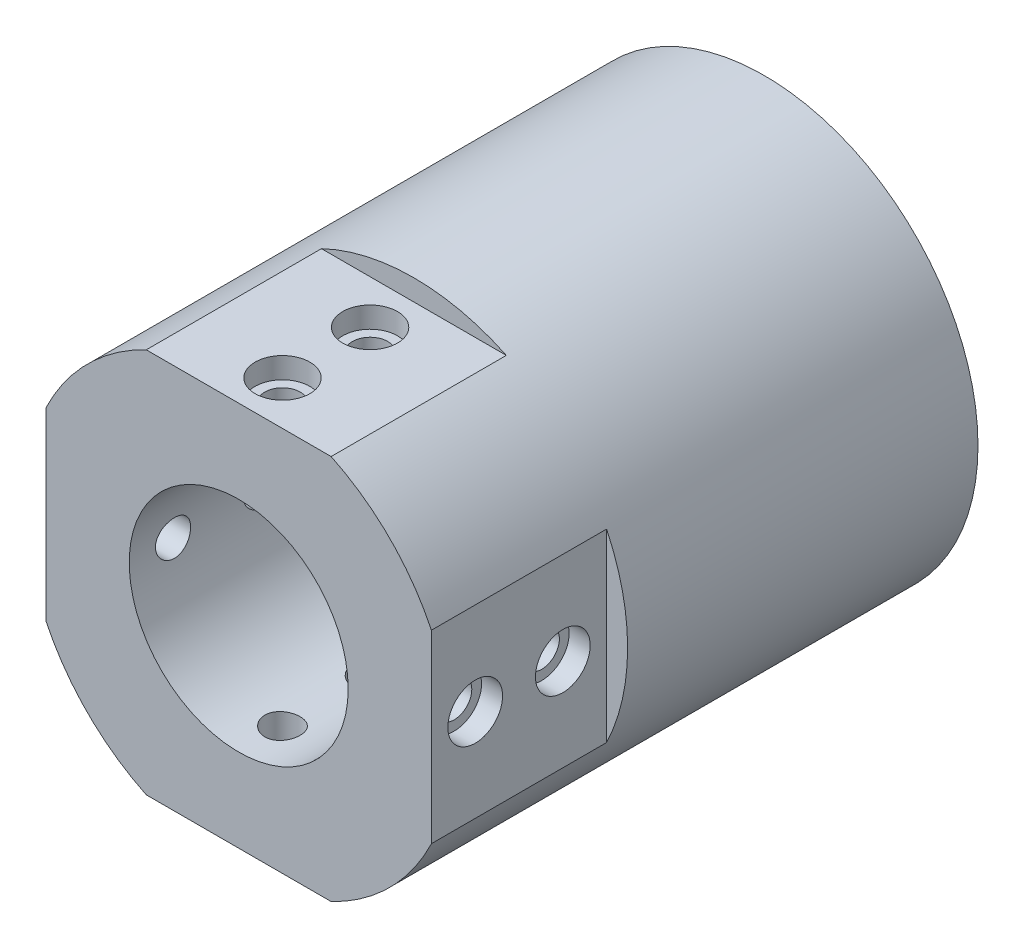
SolidWorks part; units mm, degrees
material "Brass"
ref_plane "Front Plane" through (0, 0, 0) normal (0, 0, 1) x (1, 0, 0)
ref_plane "Top Plane" through (0, 0, 0) normal (0, 1, 0) x (1, 0, 0)
ref_plane "Right Plane" through (0, 0, 0) normal (1, 0, 0) x (0, 0, -1)
sketch "Sketch1" plane through (0, 0, 0) normal (0, 0, 1) x (1, 0, 0)
  circle A0 centre (0, 0) radius 30.988
extrude "Boss-Extrude1" add sketch "Sketch1" along normal mid plane 76.2
sketch "Sketch2" plane through (0, 0, 38.1) normal (0, 0, 1) x (1, 0, 0)
  circle A0 centre (0, 0) radius 15.875
  dimension "D1" = 31.75
extrude "Cut-Extrude1" cut sketch "Sketch2" against normal blind 25.4
sketch "Sketch3" plane through (0, 0, 38.1) normal (0, 0, 1) x (1, 0, 0)
  line L1 (-27.94, -27.94) -> (27.94, -27.94)
  line L2 (-27.94, -27.94) -> (-27.94, 27.94)
  line L3 (-27.94, 27.94) -> (27.94, 27.94)
  line L4 (27.94, -27.94) -> (27.94, 27.94)
  line L5 (-27.94, -27.94) -> (27.94, 27.94) construction
  line L6 (-27.94, 27.94) -> (27.94, -27.94) construction
  circle A0 centre (0, 0) radius 30.988 construction
  point P0 (0, 0)
  dimension "D1" = 27.94
  dimension "D2" = 27.94
extrude "Cut-Extrude2" cut sketch "Sketch3" against normal blind 25.4 flip side to cut
hole_wizard "CBORE for #10 Socket Head Cap Screw1" positions "Sketch5" profile "Sketch4" counterbore size "#10" standard "ANSI Inch" end condition up to next
sketch "Sketch5" plane through (0, 27.94, 0) normal (0, 1, 0) x (1, 0, 0)
  line L0 (13.402, -38.1) -> (-13.402, -38.1) construction
  point P0 (0, -19.05)
  point P2 (0, -31.75)
  dimension "D1" = 6.35
  dimension "D2" = 12.7
sketch "Sketch4" plane through (0, 27.94, 19.05) normal (1, 0, 0) x (0, 0, 1)
  line L0 (0, 0) -> (0, 43.816)
  line L1 (0, 43.816) -> (2.5527, 43.816)
  line L3 (2.5527, 43.816) -> (2.5527, 3.048)
  line L4 (2.5527, 3.048) -> (3.9687, 3.048)
  line L5 (3.9687, 3.048) -> (3.9687, 0)
  line L7 (3.9687, 0) -> (0, 0)
  line L11 (0, -6.35) -> (0, 107.95) construction
  dimension "Thru Hole Dia." = 5.1054
  dimension "Thru Hole Depth" = 43.816
  dimension "C'Bore Dia." = 7.9375
  dimension "C'Bore Depth" = 3.048
ref_axis "Axis1" through (0, 0, 73.915) along (0, 0, -1)
pattern_circular "CirPattern1" count 4 over 360 about axis through (0, 0, 73.915) along (0, 0, -1) of "CBORE for #10 Socket Head Cap Screw1"
